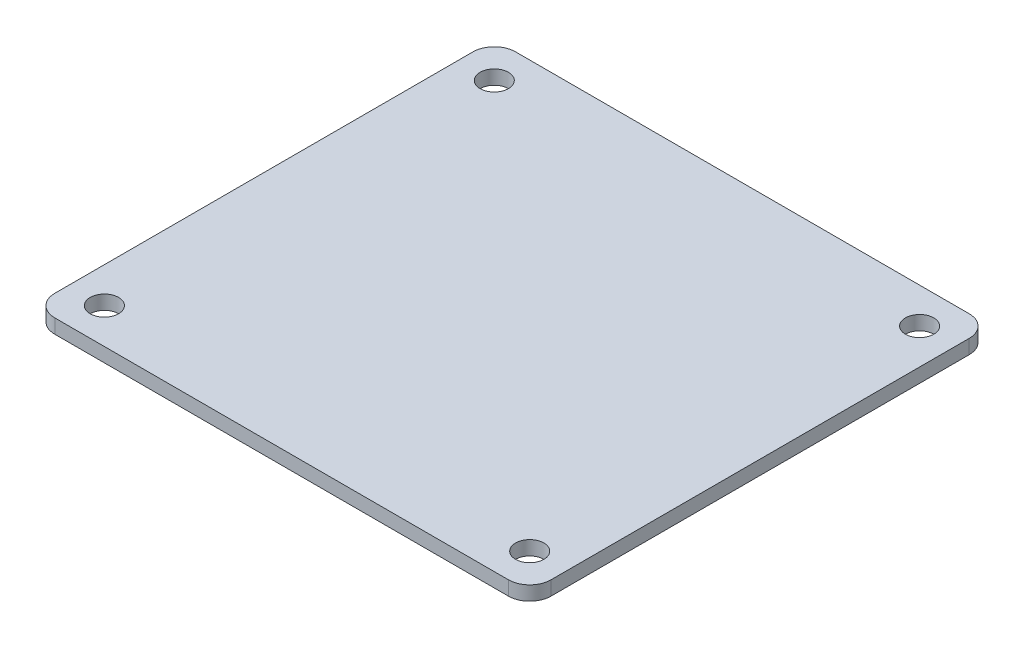
SolidWorks part; units mm, degrees
ref_plane "Front Plane" through (0, 0, 0) normal (0, 0, 1) x (1, 0, 0)
ref_plane "Top Plane" through (0, 0, 0) normal (0, 1, 0) x (1, 0, 0)
ref_plane "Right Plane" through (0, 0, 0) normal (1, 0, 0) x (0, 0, -1)
sketch "Sketch1" plane through (0, 0, 0) normal (0, 1, 0) x (1, 0, 0)
  line L1 (0, 0) -> (177.8, 0)
  line L2 (0, 0) -> (0, -165.1)
  line L3 (0, -165.1) -> (177.8, -165.1)
  line L4 (177.8, 0) -> (177.8, -165.1)
extrude "Boss-Extrude1" add sketch "Sketch1" along normal blind 5.08
ref_axis "Axis1" through (88.9, 5.08, 165.1) along (0, 0, -1)
ref_axis "Axis2" through (0, 5.08, 82.55) along (1, 0, 0)
ref_plane "Plane3" through (0, 0, 82.55) normal (0, 0, 1) x (1, 0, 0)
ref_plane "Plane4" through (88.9, 0, 0) normal (-1, 0, 0) x (0, 0, 1)
sketch "Sketch3" plane through (0, 5.08, 0) normal (0, 1, 0) x (1, 0, 0)
  circle A0 centre (12.7, -12.7) radius 5.08
extrude "Cut-Extrude1" cut sketch "Sketch3" against normal blind 5.08
mirror "Mirror1" about plane through (88.9, 0, 0) normal (-1, 0, 0) of "Cut-Extrude1"
mirror "Mirror2" about plane through (0, 0, 82.55) normal (0, 0, 1) of "Mirror1"
sketch "Sketch4" plane through (0, 0, 0) normal (0, -1, 0) x (-1, 0, 0)
  text T0 "Ben Phung & Joaquin Gonzalez-Salgado"
extrude "Cut-Extrude2" cut sketch "Sketch4" against normal blind 0.254
fillet "Fillet1" radius 7.62 4 edges at (177.8, 2.54, 165.1) (0, 2.54, 165.1) (0, 2.54, 0) (177.8, 2.54, 0)
